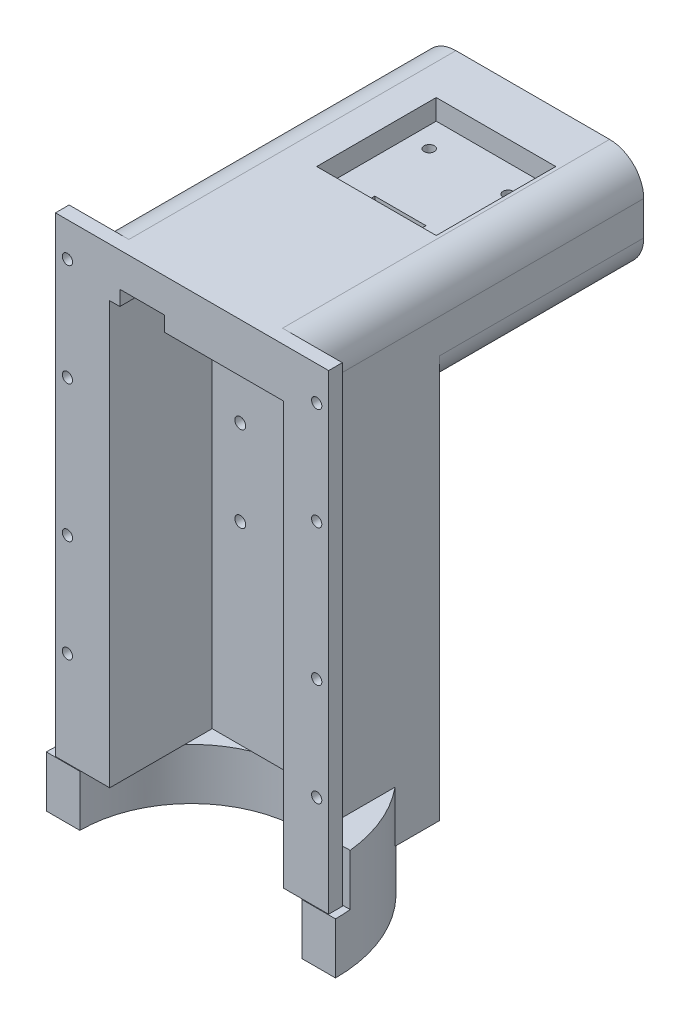
SolidWorks part; units mm, degrees
other "标注1"
sketch "草图11" plane through (0, 126.108, 100.9877) normal (-0.7402, 0.2739, 0.6141) x (-0.0038, -0.9149, 0.4036)
ref_plane "前视基准面" through (0, 0, 0) normal (0, 0, 1) x (1, 0, 0)
ref_plane "上视基准面" through (0, 0, 0) normal (0, 1, 0) x (1, 0, 0)
ref_plane "右视基准面" through (0, 0, 0) normal (1, 0, 0) x (0, 0, -1)
sketch "草图1" plane through (0, 0, 0) normal (1, 0, 0) x (0, 0, -1)
  line L1 (-100.9877, -29.9464) -> (57.7796, -29.9464)
  line L2 (-100.9877, -29.9464) -> (-100.9877, 126.0536)
  line L3 (-100.9877, 126.0536) -> (57.7796, 126.0536)
  line L4 (57.7796, -29.9464) -> (57.7796, 126.0536)
  dimension "D2" = 156
extrude "凸台-拉伸1" add sketch "草图1" along normal blind 65
sketch "草图2" plane through (65, 0, 0) normal (1, 0, 0) x (0, 0, -1)
  line L0 (-100.9877, -29.9464) -> (57.7796, -29.9464) construction
  line L1 (-60.9877, -29.9464) -> (97.8656, -29.9464)
  line L2 (-60.9877, -29.9464) -> (-60.9877, 86.0536)
  line L3 (-60.9877, 86.0536) -> (97.8656, 86.0536)
  line L4 (97.8656, -29.9464) -> (97.8656, 86.0536)
  line L5 (-100.9877, 126.0536) -> (-100.9877, -29.9464) construction
  line L7 (57.7796, 126.0536) -> (-100.9877, 126.0536) construction
  dimension "D1" = 40
  dimension "D2" = 40
extrude "切除-拉伸1" cut sketch "草图2" against normal through all
sketch "草图3" plane through (0, 0, 100.9877) normal (0, 0, 1) x (1, 0, 0)
  line L1 (8.3948, 111.7269) -> (59.3032, 111.7269)
  line L2 (8.3948, 111.7269) -> (8.3948, -33.4729)
  line L3 (8.3948, -33.4729) -> (59.3032, -33.4729)
  line L4 (59.3032, 111.7269) -> (59.3032, -33.4729)
extrude "切除-拉伸2" cut sketch "草图3" against normal blind 30
sketch "草图4" plane through (0, 126.0536, 0) normal (0, 1, 0) x (1, 0, 0)
  line L0 (65, -100.9877) -> (0, -100.9877) construction
  line L1 (19.0039, -50.9877) -> (54.0039, -50.9877)
  line L2 (19.0039, -50.9877) -> (19.0039, -15.9877)
  line L3 (19.0039, -15.9877) -> (54.0039, -15.9877)
  line L4 (54.0039, -50.9877) -> (54.0039, -15.9877)
  dimension "D1" = 50
  dimension "D2" = 35
  dimension "D3" = 35
extrude "切除-拉伸3" cut sketch "草图4" against normal blind 6
sketch "草图5" plane through (0, 120.0536, 0) normal (0, 1, 0) x (1, 0, 0)
  line L0 (19.0039, -50.9877) -> (54.0039, -50.9877) construction
  line L1 (29.0039, -50.9877) -> (44.0039, -50.9877)
  line L2 (29.0039, -50.9877) -> (29.0039, -43.9877)
  line L3 (29.0039, -43.9877) -> (44.0039, -43.9877)
  line L4 (44.0039, -50.9877) -> (44.0039, -43.9877)
  line L8 (19.0039, -15.9877) -> (19.0039, -50.9877) construction
  dimension "D1" = 7
  dimension "D2" = 15
  dimension "D3" = 10
extrude "切除-拉伸4" cut sketch "草图5" against normal blind 30
sketch "草图6" plane through (0, 0, 70.9877) normal (0, 0, 1) x (1, 0, 0)
  line L0 (59.3032, 111.7269) -> (8.3948, 111.7269) construction
  line L1 (28.3385, 111.7269) -> (44.5122, 111.7269)
  line L2 (28.3385, 111.7269) -> (28.3385, 89.9987)
  line L3 (28.3385, 89.9987) -> (44.5122, 89.9987)
  line L4 (44.5122, 111.7269) -> (44.5122, 89.9987)
extrude "切除-拉伸5" cut sketch "草图6" against normal blind 10
sketch "草图9" plane through (0, 0, -57.7796) normal (0, 0, -1) x (-1, 0, 0)
  line L1 (-59.3595, 118.5019) -> (-11.3595, 118.5019)
  line L2 (-59.3595, 118.5019) -> (-59.3595, 94.5019)
  line L3 (-59.3595, 94.5019) -> (-11.3595, 94.5019)
  line L4 (-11.3595, 118.5019) -> (-11.3595, 94.5019)
  dimension "D1" = 24
  dimension "D2" = 48
sketch "草图12" plane through (65, 0, 0) normal (1, 0, 0) x (0, 0, -1)
  line L0 (57.7796, 126.0536) -> (-100.9877, 126.0536) construction
  line L1 (-112.8966, -51.1269) -> (-26.6526, -51.1269)
  line L2 (-112.8966, -51.1269) -> (-112.8966, -11.8164)
  line L3 (-112.8966, -11.8164) -> (-26.6526, -11.8164)
  line L4 (-26.6526, -51.1269) -> (-26.6526, -11.8164)
  line L5 (-69.7746, -11.8164) -> (-69.7746, -51.1269) construction
  line L6 (-112.8966, -31.4716) -> (-26.6526, -31.4716) construction
  point P0 (-116.3149, -38.8326)
  point P4 (-24.0071, -7.0477)
  point P5 (-24.0071, -7.0477)
  point P6 (-20.3107, -9.0807)
  point P7 (119.0735, -20.3748)
  point P11 (103.8143, -13.8769)
  point P15 (-75.83, -5.9865)
  point P16 (-26.6526, -48.9249)
  point P17 (-112.8966, -51.1269)
  dimension "D1" = 137.87
extrude "切除-拉伸8" cut sketch "草图12" against normal through all
extrude "切除-拉伸6" cut sketch "草图9" against normal blind 65
sketch "草图10" plane through (0, 0, 7.2204) normal (0, 0, -1) x (-1, 0, 0)
  line L1 (-24.3595, 116.1089) -> (-11.3595, 116.1089)
  line L2 (-24.3595, 116.1089) -> (-24.3595, 94.5019)
  line L3 (-24.3595, 94.5019) -> (-11.3595, 94.5019)
  line L4 (-11.3595, 116.1089) -> (-11.3595, 94.5019)
  line L5 (-11.3595, 94.5019) -> (-11.3595, 118.5019) construction
  line L6 (-59.3595, 94.5019) -> (-11.3595, 94.5019) construction
  line L7 (-59.3595, 118.5019) -> (-59.3595, 94.5019) construction
  dimension "D1" = 35
extrude "切除-拉伸7" cut sketch "草图10" against normal blind 142
sketch "草图14" plane through (0, 126.0536, 0) normal (0, 1, 0) x (1, 0, 0)
  line L0 (65, 57.7796) -> (0, 57.7796) construction
  line L1 (-19.5236, -1.2204) -> (95.5481, -1.2204)
  line L2 (-19.5236, -1.2204) -> (-19.5236, 107.9841)
  line L3 (-19.5236, 107.9841) -> (95.5481, 107.9841)
  line L4 (95.5481, -1.2204) -> (95.5481, 107.9841)
  line L5 (38.0122, 107.9841) -> (38.0122, -1.2204) construction
  line L6 (-19.5236, 53.3818) -> (95.5481, 53.3818) construction
  point P0 (38.0122, 53.3818)
  dimension "D1" = 59
extrude "切除-拉伸9" cut sketch "草图14" against normal through all
sketch "草图16" plane through (0, 120.0536, 0) normal (0, 1, 0) x (1, 0, 0)
  line L0 (36.5039, -43.9877) -> (36.5039, -29.1874) construction
  line L1 (44.0039, -43.9877) -> (29.0039, -43.9877) construction
  line L2 (44.0039, -50.9877) -> (54.0039, -50.9877) construction
  line L3 (19.0039, -33.4877) -> (63.2223, -33.4877) construction
  line L4 (19.0039, -15.9877) -> (19.0039, -50.9877) construction
  circle A0 centre (24.9539, -46.9877) radius 1.5
  circle A1 centre (48.0539, -46.9877) radius 1.5
  circle A2 centre (24.9539, -23.9877) radius 1.5
  circle A3 centre (48.0539, -23.9877) radius 1.5
  dimension "D1" = 3
  dimension "D2" = 23.1
  dimension "D3" = 23
  dimension "D4" = 4
sketch "草图17" plane through (0, 0, 100.9877) normal (0, 0, 1) x (1, 0, 0)
  line L0 (65, 126.0536) -> (0, 126.0536) construction
  line L1 (0, -11.8164) -> (-7.5, -11.8164)
  line L2 (0, -11.8164) -> (0, 126.0536)
  line L3 (0, 126.0536) -> (-7.5, 126.0536)
  line L4 (-7.5, -11.8164) -> (-7.5, 126.0536)
  line L5 (65, -11.8164) -> (72.5, -11.8164)
  line L6 (65, -11.8164) -> (65, 126.0536)
  line L7 (65, 126.0536) -> (72.5, 126.0536)
  line L8 (72.5, -11.8164) -> (72.5, 126.0536)
  point P9 (72.5, 5.3514)
  dimension "D1" = 7.5
  dimension "D2" = 7.5
  dimension "D3" = 137.87
  dimension "D4" = 137.87
extrude "凸台-拉伸2" add sketch "草图17" against normal blind 4
extrude "切除-拉伸10" cut sketch "草图16" against normal through all
sketch "草图18" plane through (0, 86.0536, 0) normal (0, -1, 0) x (1, 0, 0)
  line L1 (-13.3339, -8.7667) -> (92.2265, -8.7667)
  line L2 (-13.3339, -8.7667) -> (-13.3339, 60.9947)
  line L3 (-13.3339, 60.9947) -> (92.2265, 60.9947)
  line L4 (92.2265, -8.7667) -> (92.2265, 60.9947)
extrude "切除-拉伸11" cut sketch "草图18" against normal blind 10
ref_plane "基准面1" through (19.0039, 126.0536, 15.9877) normal (0, 0, 1) x (1, 0, 0)
sketch "草图20" plane through (0, 96.0536, 0) normal (0, -1, 0) x (1, 0, 0)
  line L1 (24.3595, 60.9947) -> (58.6713, 60.9947)
  line L2 (24.3595, 60.9947) -> (24.3595, 11.6911)
  line L3 (24.3595, 11.6911) -> (58.6713, 11.6911)
  line L4 (58.6713, 60.9947) -> (58.6713, 11.6911)
extrude "切除-拉伸12" cut sketch "草图20" against normal blind 20
sketch "草图21" plane through (0, 0, 7.2204) normal (0, 0, -1) x (-1, 0, 0)
  circle A0 centre (-52.2003, 114.4244) radius 1.5
  circle A1 centre (-52.211, 99.9245) radius 1.5
  dimension "D1" = 3
  dimension "D2" = 14.5
extrude "切除-拉伸13" cut sketch "草图21" against normal blind 15
sketch "草图22" plane through (0, 0, 70.9877) normal (0, 0, 1) x (1, 0, 0)
  line L6 (24.3595, 111.7269) -> (58.9177, 111.7269)
  line L7 (24.3595, 111.7269) -> (24.3595, 94.6073)
  line L8 (24.3595, 94.6073) -> (58.9177, 94.6073)
  line L9 (58.9177, 111.7269) -> (58.9177, 94.6073)
extrude "切除-拉伸14" cut sketch "草图22" against normal blind 15
sketch "草图23" plane through (0, 0, 100.9877) normal (0, 0, 1) x (1, 0, 0)
  line L0 (72.5, 126.0536) -> (-7.5, 126.0536) construction
  line L1 (-7.5, 126.0536) -> (-7.5, -11.8164) construction
  line L2 (72.5, -11.8164) -> (72.5, 126.0536) construction
  circle A0 centre (69, 116.0536) radius 1.5
  circle A1 centre (69, 86.0536) radius 1.5
  circle A2 centre (69, 46.0536) radius 1.5
  circle A3 centre (69, 16.0536) radius 1.5
  circle A4 centre (-4, 116.0536) radius 1.5
  circle A5 centre (-4, 86.0536) radius 1.5
  circle A6 centre (-4, 46.0536) radius 1.5
  circle A7 centre (-4, 16.0536) radius 1.5
  dimension "D1" = 3
  dimension "D2" = 10
  dimension "D5" = 110
  dimension "D7" = 3.5
  dimension "D3" = 40
  dimension "D4" = 80
  dimension "D6" = 3.5
extrude "切除-拉伸15" cut sketch "草图23" against normal blind 15
sketch "草图24" plane through (0, -11.8164, 0) normal (0, -1, 0) x (1, 0, 0)
  line L0 (33.849, 70.9877) -> (33.849, 115.0084) construction
  line L1 (59.3032, 70.9877) -> (8.3948, 70.9877) construction
  line L2 (59.3032, 100.9877) -> (24.3595, 100.9877) construction
  circle A0 centre (32.3305, 100.9877) radius 32.5
  circle A1 centre (32.3305, 100.9877) radius 42.3454
  dimension "D1" = 65
sketch "草图28" plane through (0, 0, 70.9877) normal (0, 0, 1) x (1, 0, 0)
  circle A0 centre (16.6227, 69.8238) radius 1.6
  circle A2 centre (52.1827, 69.8238) radius 1.6
  circle A3 centre (16.6227, 44.8038) radius 1.6
  circle A4 centre (52.1827, 44.8038) radius 1.6
  point P4 (0, 0)
  point P7 (45.6171, 46.88)
  point P8 (16.6206, 25.8113)
  point P11 (47.0602, 24.4836)
  point P12 (0, 0)
  point P13 (0, 0)
  point P14 (50.0836, 48.9723)
  point P15 (0, 0)
  dimension "D1" = 3.2
  dimension "D2" = 35.56
  dimension "D3" = 25.02
extrude "切除-拉伸17" cut sketch "草图28" against normal blind 10
fillet "圆角5" radius 10 2 edges at (0, 126.0536, 49.104) (65, 126.0536, 49.104)
fillet "圆角6" radius 10 2 edges at (65, 96.0536, 31.1076) (0, 96.0536, 31.1076)
extrude "凸台-拉伸3" add sketch "草图24" along normal blind 15
sketch "草图29" plane through (0, -11.8164, 0) normal (0, 1, 0) x (1, 0, 0)
  line L0 (0, -73.6405) -> (0, -96.7845)
  line L1 (-9.8057, -96.7845) -> (0, -96.7845)
  arc A0 (0, -73.6405) -> (-9.8057, -96.7845) centre (32.3305, -100.9877) ccw
  arc A1 (0, -73.6405) -> (65, -74.0463) centre (32.3305, -100.9877) ccw construction
extrude "凸台-拉伸4" add sketch "草图29" along normal blind 15
sketch "草图30" plane through (0, -11.8164, 0) normal (0, 1, 0) x (1, 0, 0)
  line L0 (74.4493, -96.6128) -> (65, -96.9877)
  line L1 (65, -74.0463) -> (65, -96.9877) construction
  line L2 (72.5, -96.9877) -> (55, -96.9877) construction
  line L3 (65, -74.0463) -> (65, -96.9877)
  arc A0 (65, -74.0463) -> (74.4493, -96.6128) centre (32.3305, -100.9877) cw
  arc A1 (-9.8057, -96.7845) -> (65, -74.0463) centre (32.3305, -100.9877) ccw construction
extrude "凸台-拉伸5" add sketch "草图30" along normal blind 15
sketch "草图31" plane through (0, -11.8164, 0) normal (0, 1, 0) x (1, 0, 0)
  line L1 (-19.6781, -151.5247) -> (113.2939, -151.5247)
  line L2 (-19.6781, -151.5247) -> (-19.6781, -101.1628)
  line L3 (-19.6781, -101.1628) -> (113.2939, -101.1628)
  line L4 (113.2939, -151.5247) -> (113.2939, -101.1628)
extrude "切除-拉伸18" cut sketch "草图31" against normal blind 15
